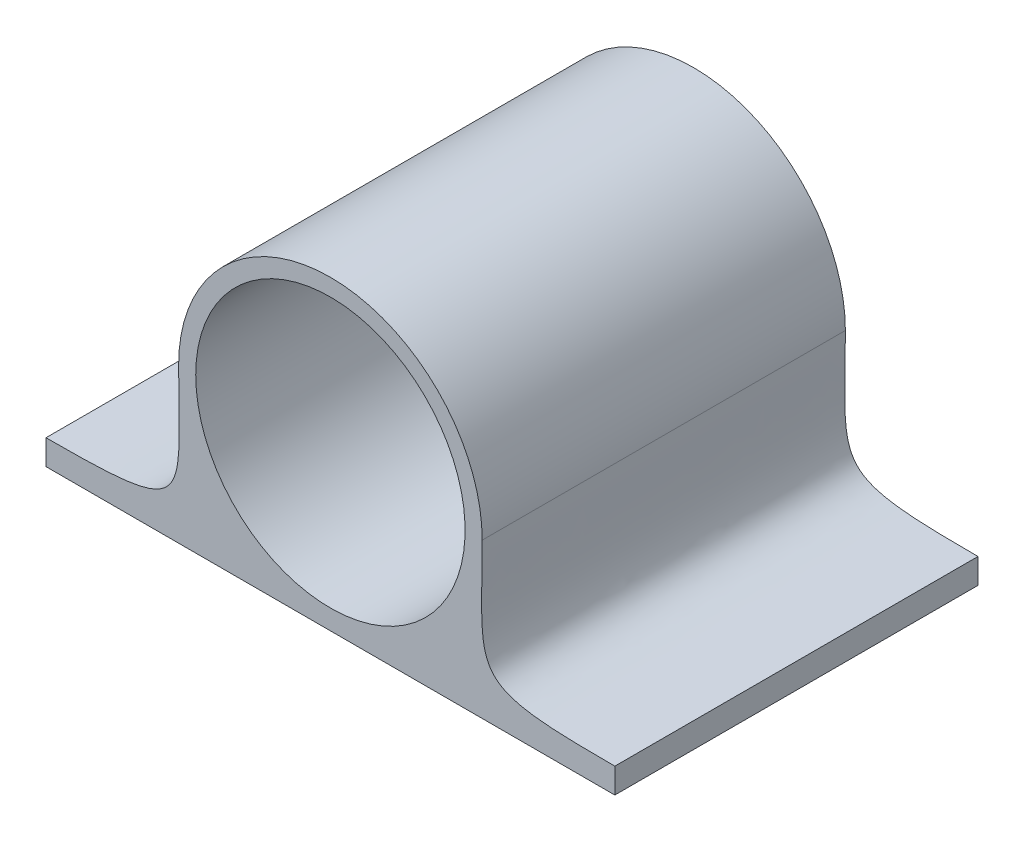
SolidWorks part; units mm, degrees
ref_plane "Front Plane" through (0, 0, 0) normal (0, 0, 1) x (1, 0, 0)
ref_plane "Top Plane" through (0, 0, 0) normal (0, 1, 0) x (1, 0, 0)
ref_plane "Right Plane" through (0, 0, 0) normal (1, 0, 0) x (0, 0, -1)
sketch "Sketch1" plane through (0, 0, 0) normal (0, 0, 1) x (1, 0, 0)
  line L0 (-45.4219, -24.6662) -> (45.4219, -24.6662)
  line L1 (-45.4219, -20.6662) -> (-45.4219, -24.6662)
  line L2 (0, 0) -> (0, -11.8779)
  line L3 (45.4219, -20.6662) -> (45.4219, -24.6662)
  circle A0 centre (0, 0) radius 21.51
  circle A1 centre (0, 0) radius 24.2415
  circle A2 centre (0, 0) radius 5.15
  spline S0 degree 3 poles (-45.4219, -20.6662) (-21.5322, -20.6662) (-24.2415, -19.0788) (-24.2415, 0) knots 0 0 0 0 1 1 1 1
  spline S2 degree 3 poles (45.4219, -20.6662) (21.5322, -20.6662) (24.2415, -19.0788) (24.2415, 0) knots 0 0 0 0 1 1 1 1
  point P7 (0, 0)
  point P11 (0, -24.6662)
extrude "Boss-Extrude1" add sketch "Sketch1" along normal blind 58 contours A1 A0 | L3 S2 A1 S0 L1 L0 region at (-44.4806, -22.6662, 0) region at (0, 23.5558, 0)
extrude "Boss-Extrude2" add sketch "Sketch1<4>" along normal blind 3 contours A0 region at (-20.9016, 0, 0)
sketch "Sketch1<4>" plane through (0, 0, 0) normal (0, 0, 1) x (1, 0, 0) same geometry as "Sketch1"
sketch "Sketch2" plane through (0, 0, 0) normal (0, 1, 0) x (1, 0, 0)
  line L0 (-24.1489, 0) -> (-45.4219, 0) construction
  line L1 (-45.4219, -58) -> (-45.4219, 0) construction
  circle A0 centre (-40.4219, -5) radius 2
  point P14 (0, -29.0869)
  dimension "D1" = 5
  dimension "D2" = 5
